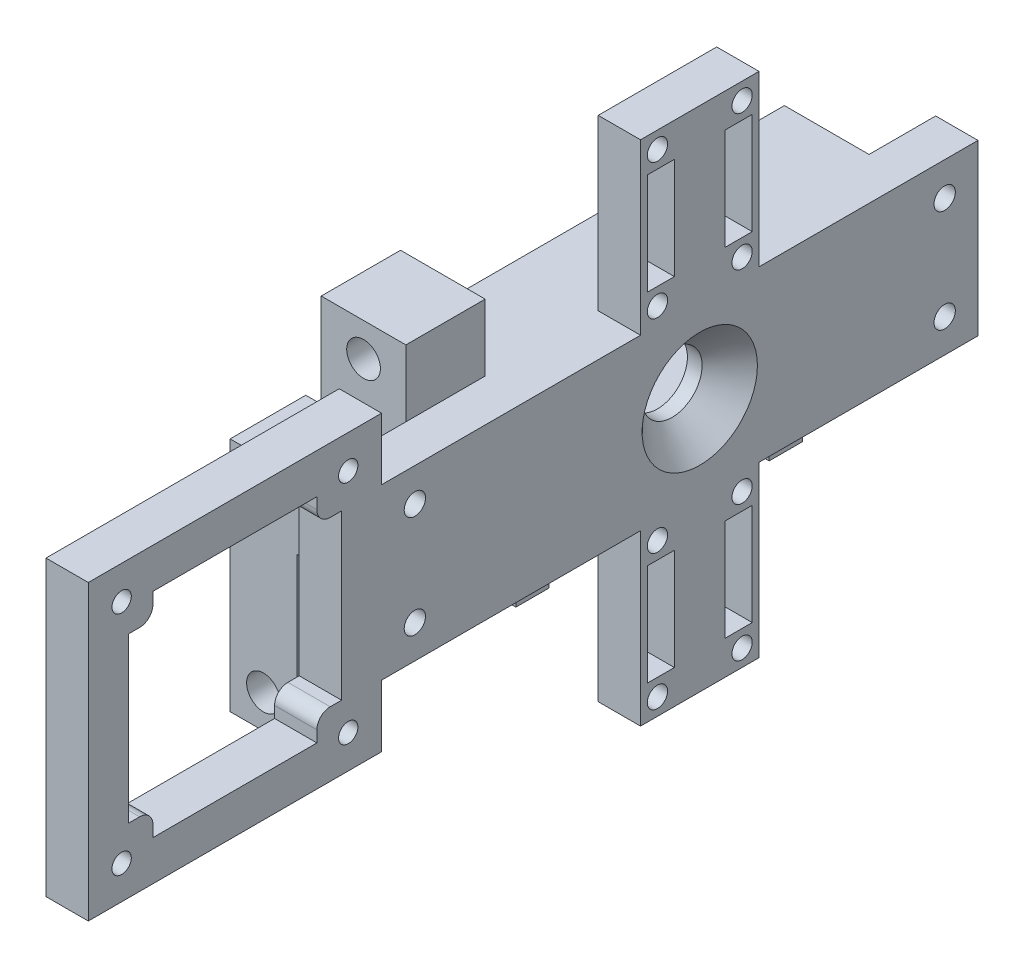
SolidWorks part; units mm, degrees
ref_plane "Front Plane" through (0, 0, 0) normal (0, 0, 1) x (1, 0, 0)
ref_plane "Top Plane" through (0, 0, 0) normal (0, 1, 0) x (1, 0, 0)
ref_plane "Right Plane" through (0, 0, 0) normal (1, 0, 0) x (0, 0, -1)
sketch "Sketch1" plane through (0, 0, 0) normal (0, 1, 0) x (1, 0, 0)
  line L1 (0, 0) -> (6.35, 0)
  line L2 (0, 0) -> (0, 89.5)
  line L3 (0, 89.5) -> (6.35, 89.5)
  line L4 (6.35, 0) -> (6.35, 89.5)
  dimension "D1" = 89.5
  dimension "D2" = 6.35
extrude "Boss-Extrude1" add sketch "Sketch1" along normal blind 25.4
sketch "Sketch2" plane through (0, 0, 0) normal (-1, 0, 0) x (0, 0, 1)
  line L0 (-89.5, 25.4) -> (0, 25.4) construction
  line L1 (-74.15, 20.05) -> (-21.35, 20.05)
  line L2 (-74.15, 20.05) -> (-74.15, 5.35)
  line L3 (-74.15, 5.35) -> (-21.35, 5.35)
  line L4 (-21.35, 20.05) -> (-21.35, 5.35)
  line L6 (-89.5, 25.4) -> (-89.5, 0) construction
  line L13 (-89.5, 0) -> (0, 0) construction
  line L14 (-79.5, 25.4) -> (-10, 25.4)
  line L15 (-79.5, 25.4) -> (-79.5, 0)
  line L16 (-79.5, 0) -> (-10, 0)
  line L17 (-10, 25.4) -> (-10, 0)
  line L18 (0, 25.4) -> (0, 0) construction
  dimension "D1" = 52.8
  dimension "D2" = 14.7
  dimension "D3" = 5.35
  dimension "D4" = 15.35
  dimension "D5" = 10
  dimension "D6" = 10
sketch "Sketch4" plane through (6.35, 0, 0) normal (1, 0, 0) x (0, 0, -1)
  line L0 (0, 25.4) -> (0, 0) construction
  line L1 (0, 34.7) -> (-44, 34.7)
  line L2 (0, 34.7) -> (0, -9.3)
  line L3 (0, -9.3) -> (-44, -9.3)
  line L4 (-44, 34.7) -> (-44, -9.3)
  line L6 (0, 25.4) -> (89.5, 25.4) construction
  circle A0 centre (-39, 29.7) radius 1.45
  circle A1 centre (-5, 29.7) radius 1.45
  circle A2 centre (-39, -4.3) radius 1.45
  circle A3 centre (-5, -4.3) radius 1.45
  dimension "D4" = 34
  dimension "D6" = 2.9
  dimension "D7" = 34
  dimension "D1" = 44
  dimension "D2" = 9.3
  dimension "D3" = 44
  dimension "D5" = 5
  dimension "D8" = 5
extrude "Boss-Extrude2" add sketch "Sketch4" against normal up to surface (6.35 mm away) up to face at (0, 12.7, -44.75)
hole_wizard "CSK for M8 Flat Head Machine Screw1" positions "Sketch6" profile "Sketch7" countersink size "M8" standard "ANSI Metric"
sketch "Sketch6" plane through (6.35, 0, 0) normal (1, 0, 0) x (0, 0, -1)
  line L1 (89.5, 25.4) -> (89.5, 0) construction
  line L2 (0, 25.4) -> (89.5, 25.4) construction
  point P0 (47.75, 12.7)
  dimension "D1" = 41.75
  dimension "D2" = 12.7
sketch "Sketch7" plane through (6.35, 12.7, -47.75) normal (0, 1, 0) x (0, 0, -1)
  line L0 (0, 0) -> (0, 20.2039)
  line L1 (0, 20.2039) -> (4.5, 17.5)
  line L2 (4.5, 17.5) -> (4.5, 4.15)
  line L3 (4.5, 4.15) -> (8.65, 0)
  line L5 (8.65, 0) -> (0, 0)
  line L6 (-4.5, 4.15) -> (-8.65, 0) construction
  line L10 (0, 20.2039) -> (-4.5, 17.5) construction
  line L11 (0, -6.35) -> (0, 107.95) construction
  dimension "Hole Dia." = 9
  dimension "Hole Depth" = 17.5
  dimension "Near C'Sink Dia." = 17.3
  dimension "Near C'Sink Angle" = 90
  dimension "Drill Angle" = 118
extrude "Boss-Extrude3" add sketch "Sketch2" along normal blind 12.7
sketch "Sketch9" plane through (0, 0, 0) normal (-1, 0, 0) x (0, 0, 1)
  line L1 (0, 34.7) -> (0, 25.4) construction
  line L2 (-10, 25.4) -> (0, 25.4) construction
  line L3 (-10, 0) -> (0, 0) construction
  line L4 (-89.5, 25.4) -> (-89.5, 0) construction
  circle A0 centre (-5, 20.4) radius 1.6
  circle A1 centre (-5, 5) radius 1.6
  circle A3 centre (-84.5, 5) radius 1.6
  circle A4 centre (-84.5, 20.4) radius 1.6
  dimension "D1" = 3.2
  dimension "D2" = 5
  dimension "D3" = 5
  dimension "D4" = 5
  dimension "D5" = 5
extrude "Cut-Extrude1" cut sketch "Sketch9" against normal up to surface (6.35 mm away) up to face at (6.35, 12.7, -56.4)
sketch "Sketch10" plane through (6.35, 0, 0) normal (1, 0, 0) x (0, 0, -1)
  line L0 (0, 25.4) -> (89.5, 25.4) construction
  line L1 (38.86, 25.4) -> (56.64, 25.4)
  line L2 (38.86, 25.4) -> (38.86, 50.8)
  line L3 (38.86, 50.8) -> (56.64, 50.8)
  line L4 (56.64, 25.4) -> (56.64, 50.8)
  line L5 (89.5, 25.4) -> (89.5, 0) construction
  line L7 (0, 0) -> (89.5, 0) construction
  line L8 (38.86, 0) -> (56.64, 0)
  line L9 (38.86, 0) -> (38.86, -25.4)
  line L10 (38.86, -25.4) -> (56.64, -25.4)
  line L11 (56.64, 0) -> (56.64, -25.4)
  circle A0 centre (41.4, 27.94) radius 1.524
  circle A1 centre (54.1, 27.94) radius 1.524
  circle A2 centre (54.1, 48.26) radius 1.524
  circle A3 centre (41.4, 48.26) radius 1.524
  circle A4 centre (41.4, -2.54) radius 1.524
  circle A5 centre (54.1, -2.54) radius 1.524
  circle A6 centre (41.4, -22.86) radius 1.524
  circle A7 centre (54.1, -22.86) radius 1.524
  point P25 (47.75, 50.8)
  dimension "D3" = 3.048
  dimension "D11" = 2.54
  dimension "D1" = 25.4
  dimension "D2" = 17.78
  dimension "D4" = 20.32
  dimension "D5" = 12.7
  dimension "D6" = 2.54
  dimension "D7" = 2.54
  dimension "D8" = 41.75
  dimension "D9" = 25.4
  dimension "D10" = 17.78
  dimension "D12" = 20.32
extrude "Boss-Extrude4" add sketch "Sketch10" against normal blind 6.35
sketch "Sketch11" plane through (6.35, 0, 0) normal (1, 0, 0) x (0, 0, -1)
  line L0 (0, 0) -> (38.86, 0) construction
  line L1 (39.876, -5.08) -> (43.94, -5.08)
  line L2 (39.876, -5.08) -> (39.876, -20.32)
  line L3 (39.876, -20.32) -> (43.94, -20.32)
  line L4 (43.94, -5.08) -> (43.94, -20.32)
  line L5 (51.56, -5.08) -> (55.624, -5.08)
  line L6 (51.56, -5.08) -> (51.56, -20.32)
  line L7 (51.56, -20.32) -> (55.624, -20.32)
  line L8 (55.624, -5.08) -> (55.624, -20.32)
  line L9 (38.86, -25.4) -> (56.64, -25.4) construction
  line L10 (38.86, 0) -> (38.86, -25.4) construction
  line L11 (56.64, -25.4) -> (56.64, 0) construction
  line L12 (56.64, 50.8) -> (38.86, 50.8) construction
  line L13 (39.876, 45.72) -> (43.94, 45.72)
  line L14 (39.876, 45.72) -> (39.876, 30.48)
  line L15 (39.876, 30.48) -> (43.94, 30.48)
  line L16 (43.94, 45.72) -> (43.94, 30.48)
  line L17 (51.56, 45.72) -> (55.624, 45.72)
  line L18 (51.56, 45.72) -> (51.56, 30.48)
  line L19 (51.56, 30.48) -> (55.624, 30.48)
  line L20 (55.624, 45.72) -> (55.624, 30.48)
  line L21 (0, 25.4) -> (38.86, 25.4) construction
  dimension "D1" = 5.08
  dimension "D2" = 5.08
  dimension "D3" = 1.016
  dimension "D4" = 4.064
  dimension "D5" = 1.016
  dimension "D6" = 5.08
  dimension "D7" = 5.08
extrude "Cut-Extrude2" cut sketch "Sketch11" against normal up to surface (6.35 mm away) up to face at (0, -22.86, -55.624)
sketch "Sketch14" plane through (0, 25.4, 0) normal (0, 1, 0) x (1, 0, 0)
  line L0 (-12.7, 10) -> (-12.7, 79.5) construction
  line L1 (0, 10) -> (-12.7, 10)
  line L2 (0, 10) -> (0, 21.9)
  line L3 (0, 21.9) -> (-12.7, 21.9)
  line L4 (-12.7, 10) -> (-12.7, 21.9)
  dimension "D1" = 11.9
extrude "Boss-Extrude5" add sketch "Sketch14" along normal blind 10
sketch "Sketch15" plane through (0, 0, -10) normal (0, 0, 1) x (1, 0, 0)
  line L0 (-12.7, 0) -> (-12.7, 35.4) construction
  line L1 (-12.7, 35.4) -> (0, 35.4) construction
  circle A0 centre (-6.35, 30.4) radius 2.5273
  dimension "D1" = 6.35
  dimension "D2" = 5.0546
  dimension "D3" = 5
extrude "Cut-Extrude4" cut sketch "Sketch15" against normal blind 7
sketch "Sketch16" plane through (-12.7, 0, 0) normal (-1, 0, 0) x (0, 0, 1)
  line L0 (-10, 0) -> (-10, 35.4) construction
  line L1 (-10, 10) -> (-21.35, 10)
  line L2 (-10, 10) -> (-10, 0)
  line L3 (-10, 0) -> (-21.35, 0)
  line L4 (-21.35, 10) -> (-21.35, 0)
  line L5 (-79.5, 0) -> (-10, 0) construction
  dimension "D1" = 10
  dimension "D2" = 11.35
extrude "Boss-Extrude6" add sketch "Sketch16" along normal blind 13.6718
sketch "Sketch17" plane through (0, 0, 0) normal (0, -1, 0) x (1, 0, 0)
  line L0 (-26.3718, -21.35) -> (-12.7, -21.35) construction
  line L1 (-26.3718, -10) -> (-16.3718, -10)
  line L2 (-26.3718, -10) -> (-26.3718, -21.35)
  line L3 (-26.3718, -21.35) -> (-16.3718, -21.35)
  line L4 (-16.3718, -10) -> (-16.3718, -21.35)
  dimension "D1" = 10
extrude "Boss-Extrude7" add sketch "Sketch17" along normal blind 25.4523
sketch "Sketch18" plane through (0, 0, -10) normal (0, 0, 1) x (1, 0, 0)
  line L0 (-16.3718, -25.4523) -> (-26.3718, -25.4523) construction
  line L1 (-26.3718, -25.4523) -> (-26.3718, 10) construction
  circle A0 centre (-21.3718, -20.4523) radius 2.5273
  circle A1 centre (-6.35, 30.4) radius 2.5273 construction
  dimension "D1" = 5
  dimension "D2" = 5
extrude "Cut-Extrude5" cut sketch "Sketch18" against normal blind 7
sketch "Sketch19" plane through (0, 0, 0) normal (0, -1, 0) x (1, 0, 0)
  line L0 (-12.7, -79.5) -> (-12.7, -21.35) construction
  line L1 (-12.7, -47.925) -> (-18.0384, -47.925)
  line L2 (-12.7, -47.925) -> (-12.7, -57.925)
  line L3 (-12.7, -57.925) -> (-18.0384, -57.925)
  line L4 (-18.0384, -47.925) -> (-18.0384, -57.925)
  line L5 (-16.3718, -21.35) -> (-12.7, -21.35) construction
  dimension "D1" = 10
  dimension "D2" = 26.575
  dimension "D3" = 5.3384
extrude "Boss-Extrude8" add sketch "Sketch19" against normal up to surface (5.35 mm away) up to face at (-6.35, 5.35, -47.75)
sketch "Sketch21" plane through (0, 0, 0) normal (0, -1, 0) x (1, 0, 0)
  line L0 (-12.7, -47.925) -> (-12.7, -21.35) construction
  line L1 (-18.0384, -47.925) -> (-12.7, -47.925)
  line L2 (-18.0384, -47.925) -> (-18.0384, -57.925)
  line L3 (-18.0384, -57.925) -> (-12.7, -57.925)
  line L4 (-12.7, -47.925) -> (-12.7, -57.925)
  line L5 (-12.7, -31.425) -> (-4.9108, -31.425)
  line L6 (-12.7, -31.425) -> (-12.7, -36.425)
  line L7 (-12.7, -36.425) -> (-4.9108, -36.425)
  line L8 (-4.9108, -31.425) -> (-4.9108, -36.425)
  line L9 (-12.7, -79.5) -> (-12.7, -57.925) construction
  line L10 (-12.7, -69.425) -> (-4.9108, -69.425)
  line L11 (-12.7, -69.425) -> (-12.7, -74.425)
  line L12 (-12.7, -74.425) -> (-4.9108, -74.425)
  line L13 (-4.9108, -69.425) -> (-4.9108, -74.425)
  point P12 (-12.7, -52.925)
  point P19 (-15.3692, -47.925)
  dimension "D1" = 21.5
  dimension "D2" = 10.4584
  dimension "D3" = 5
  dimension "D4" = 43
  dimension "D5" = 5
extrude "Boss-Extrude9" add sketch "Sketch21" along normal blind 11.85
sketch "Sketch22" plane through (0, -11.85, 0) normal (0, -1, 0) x (1, 0, 0)
  line L0 (-12.7, -47.925) -> (-18.0384, -47.925) construction
  line L1 (-18.0384, -47.925) -> (-18.0384, -57.925) construction
  circle A0 centre (-12.5308, -52.925) radius 2.5273
  dimension "D1" = 5
  dimension "D3" = 5.0546
  dimension "D2" = 5.5076
sketch "Sketch23" plane through (-12.7, 0, 0) normal (1, 0, 0) x (0, 0, -1)
  line L1 (47.925, 0) -> (57.925, 0)
  line L2 (47.925, 0) -> (47.925, -11.85)
  line L3 (47.925, -11.85) -> (57.925, -11.85)
  line L4 (57.925, 0) -> (57.925, -11.85)
extrude "Boss-Extrude10" add sketch "Sketch23" along normal blind 4.6616
extrude "Cut-Extrude6" cut sketch "Sketch22" against normal blind 7
sketch "Sketch25" plane through (-18.0384, 0, 0) normal (-1, 0, 0) x (0, 0, 1)
  line L5 (-47.925, 5.35) -> (-47.925, -11.85) construction
  line L6 (-57.925, 5.35) -> (-47.925, 5.35)
  line L7 (-57.925, 5.35) -> (-57.925, 0)
  line L8 (-57.925, 0) -> (-47.925, 0)
  line L9 (-47.925, 5.35) -> (-47.925, 0)
  line L10 (-56.64, 0) -> (-38.86, 0) construction
extrude "Cut-Extrude7" cut sketch "Sketch25" against normal up to surface (5.3384 mm away) up to face at (-12.7, 10.5437, -51.0844)
sketch "Sketch26" plane through (6.35, 0, 0) normal (1, 0, 0) x (0, 0, -1)
  line L23 (-34.3, 28.7) -> (-9.7, 28.7)
  line L26 (-38, 25) -> (-38, 0.4)
  line L27 (-34.3, -3.3) -> (-9.7, -3.3)
  line L28 (-6, 25) -> (-6, 0.4)
  line L30 (-44, 34.7) -> (-44, -9.3) construction
  line L31 (-44, -9.3) -> (0, -9.3) construction
  line L33 (-34.3, 28.7) -> (-34.3, 25)
  line L34 (-38, 25) -> (-34.3, 25)
  line L35 (-9.7, 28.7) -> (-9.7, 25)
  line L36 (-9.7, 25) -> (-6, 25)
  line L37 (-6, 0.4) -> (-9.7, 0.4)
  line L38 (-9.7, 0.4) -> (-9.7, -3.3)
  line L39 (-38, 0.4) -> (-34.3, 0.4)
  line L40 (-34.3, 0.4) -> (-34.3, -3.3)
  line L41 (0, 25.4) -> (0, 34.7) construction
  line L42 (0, 34.7) -> (-44, 34.7) construction
  dimension "D5" = 3.7
  dimension "D6" = 3.7
  dimension "D9" = 3.7
  dimension "D11" = 3.7
  dimension "D7" = 6
  dimension "D2" = 3.7
  dimension "D3" = 6
  dimension "D4" = 6
  dimension "D8" = 3.7
  dimension "D10" = 3.7
  dimension "D12" = 6
extrude "Cut-Extrude8" cut sketch "Sketch26" against normal up to surface (6.35 mm away) up to face at (0, 5, -3.4)
fillet "Fillet1" radius 2 4 edges at (3.175, 25, 9.7) (3.175, 0.4, 34.3) (3.175, 0.4, 9.7) (3.175, 25, 34.3)
equation "\"D1@Cut-Extrude4\"=4"
